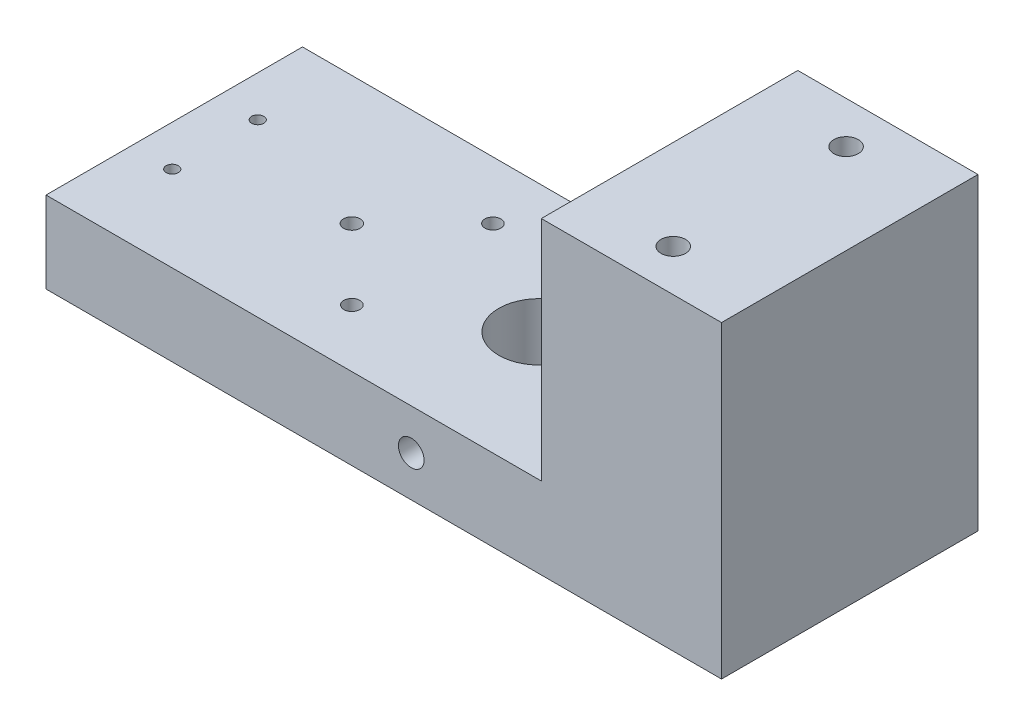
SolidWorks part; units mm, degrees
material "1060 Alloy"
ref_plane "Front Plane" through (0, 0, 0) normal (0, 0, 1) x (1, 0, 0)
ref_plane "Top Plane" through (0, 0, 0) normal (0, 1, 0) x (1, 0, 0)
ref_plane "Right Plane" through (0, 0, 0) normal (1, 0, 0) x (0, 0, -1)
sketch "Sketch2" plane through (0, 0, 0) normal (1, 0, 0) x (0, 0, -1)
  line L1 (-28.0311, -10.8164) -> (11.9689, -10.8164)
  line L2 (-28.0311, -10.8164) -> (-28.0311, 1.8836)
  line L3 (-28.0311, 1.8836) -> (11.9689, 1.8836)
  line L4 (11.9689, -10.8164) -> (11.9689, 1.8836)
  dimension "D1" = 12.7
  dimension "D2" = 40
extrude "Boss-Extrude1" add sketch "Sketch2" along normal blind 105.35
sketch "Sketch4" plane through (0, 1.8836, 0) normal (0, 1, 0) x (1, 0, 0)
  line L5 (0, 11.9689) -> (0, -28.0311) construction
  line L6 (105.35, 11.9689) -> (0, 11.9689) construction
  circle A0 centre (56.96, -8.0311) radius 6.35
  dimension "D1" = 20
  dimension "D3" = 56.96
  dimension "D2" = 12.7
extrude "Cut-Extrude1" cut sketch "Sketch4" against normal through all
hole_wizard "Ø4.0 (4) Diameter Hole1" positions "Sketch7" profile "Sketch6" hole size "Ø4.0" standard "ANSI Metric" end condition through all
sketch "Sketch7" plane through (0, 0, 28.0311) normal (0, 0, 1) x (1, 0, 0)
  line L0 (0, 1.8836) -> (0, -10.8164) construction
  line L3 (105.35, 1.8836) -> (0, 1.8836) construction
  point P0 (56.96, -4.4664)
  point P1 (0, -4.4664)
  dimension "D1" = 56.96
  dimension "D3" = 6.35
sketch "Sketch6" plane through (56.96, -4.4664, 28.0311) normal (1, 0, 0) x (0, -1, 0)
  line L0 (0, 0) -> (0, 40)
  line L1 (0, 40) -> (2, 40)
  line L2 (2, 40) -> (2, 0)
  line L5 (2, 0) -> (0, 0)
  line L11 (0, -6.35) -> (0, 107.95) construction
  dimension "Thru Hole Dia." = 4
  dimension "Thru Hole Depth" = 40
sketch "Sketch9" plane through (0, 1.8836, 0) normal (0, 1, 0) x (1, 0, 0)
  line L0 (0, 11.9689) -> (0, -28.0311) construction
  line L2 (105.35, -28.0311) -> (0, -28.0311) construction
  circle A0 centre (27.7, -8.0311) radius 1.2915
  circle A2 centre (38.7, 2.9689) radius 1.25
  circle A3 centre (38.7, -19.0311) radius 1.25
  dimension "D2" = 2.5
  dimension "D3" = 20
  dimension "D4" = 2.5
  dimension "D1" = 27.7
  dimension "D6" = 11
  dimension "D7" = 11
  dimension "D8" = 22
  dimension "D9" = 11
extrude "Cut-Extrude3" cut sketch "Sketch9" against normal through all
sketch "Sketch14" plane through (0, 1.8836, 0) normal (0, 1, 0) x (1, 0, 0)
  line L0 (105.35, -28.0311) -> (0, -28.0311) construction
  line L1 (105.35, -28.0311) -> (77.25, -28.0311)
  line L2 (105.35, -28.0311) -> (105.35, 11.9689)
  line L3 (105.35, 11.9689) -> (77.25, 11.9689)
  line L4 (77.25, -28.0311) -> (77.25, 11.9689)
  line L5 (105.35, 11.9689) -> (0, 11.9689) construction
  dimension "D1" = 28.1
extrude "Boss-Extrude3" add sketch "Sketch14" along normal blind 35.45
sketch "Sketch10" plane through (0, -10.8164, 0) normal (0, 1, 0) x (1, 0, 0)
  line L0 (105.35, 11.9689) -> (105.35, -28.0311) construction
  line L2 (105.35, 11.9689) -> (0, 11.9689) construction
  line L3 (105.35, -28.0311) -> (0, -28.0311) construction
  circle A0 centre (91.3, -21.5058) radius 3.75
  circle A1 centre (91.3, 5.4436) radius 3.75
  dimension "D1" = 7.5
  dimension "D2" = 7.5
  dimension "D7" = 6.5253
  dimension "D8" = 6.5253
  dimension "D4" = 14.05
  dimension "D5" = 14.05
extrude "Cut-Extrude4" cut sketch "Sketch10" along normal blind 24.5
sketch "Sketch15" plane through (0, 13.6836, 0) normal (0, -1, 0) x (1, 0, 0)
  circle A0 centre (91.3, -5.4436) radius 1.905
  circle A1 centre (91.3, 21.5058) radius 1.905
  dimension "D1" = 3.81
  dimension "D2" = 3.81
extrude "Cut-Extrude7" cut sketch "Sketch15" against normal through all
sketch "Sketch17" plane through (0, -10.8164, 0) normal (0, -1, 0) x (1, 0, 0)
  line L0 (105.35, 28.0311) -> (0, 28.0311) construction
  line L1 (105.35, -11.9689) -> (0, -11.9689) construction
  line L2 (0, 28.0311) -> (0, -11.9689) construction
  circle A0 centre (6.35, 14.6981) radius 0.95
  circle A1 centre (6.35, 1.3641) radius 0.95
  dimension "D1" = 1.9
  dimension "D2" = 1.9
  dimension "D3" = 13.333
  dimension "D4" = 13.333
  dimension "D5" = 6.35
  dimension "D6" = 6.35
extrude "Cut-Extrude8" cut sketch "Sketch17" against normal blind 21
